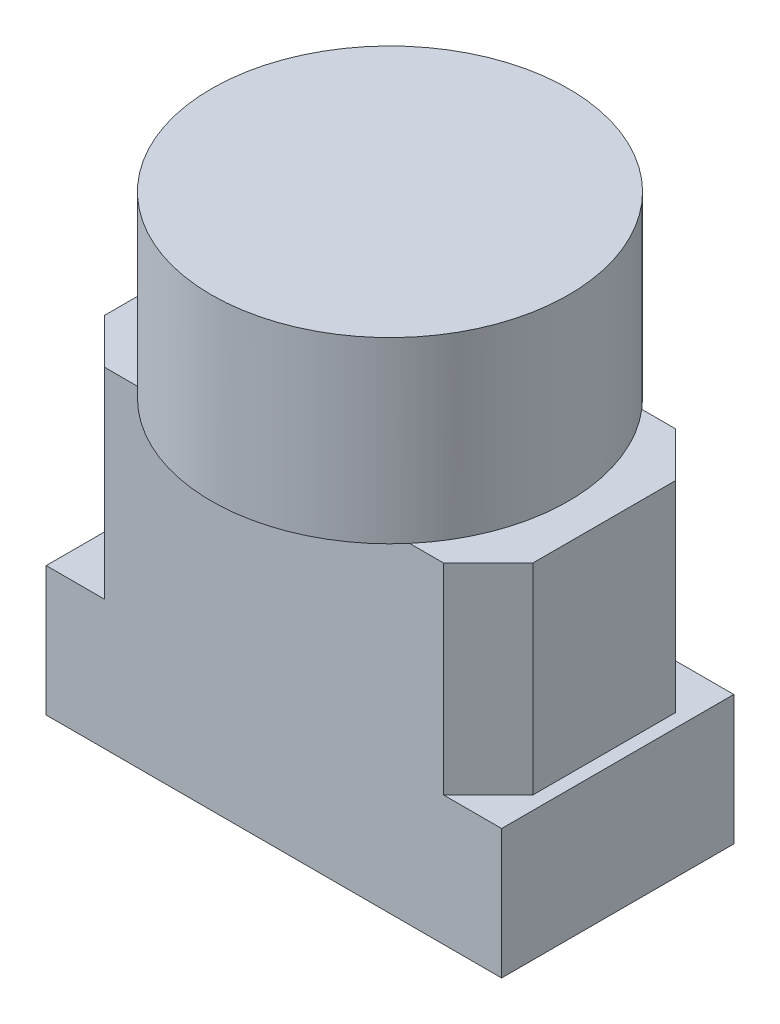
SolidWorks part; units mm, degrees
material "1060 Alloy"
ref_plane "Front Plane" through (0, 0, 0) normal (0, 0, 1) x (1, 0, 0)
ref_plane "Top Plane" through (0, 0, 0) normal (0, 1, 0) x (1, 0, 0)
ref_plane "Right Plane" through (0, 0, 0) normal (1, 0, 0) x (0, 0, -1)
sketch "Sketch1" plane through (0, 0, 0) normal (0, 1, 0) x (1, 0, 0)
  circle A0 centre (0, 0) radius 40
  dimension "D1" = 80
extrude "Boss-Extrude1" add sketch "Sketch1" along normal blind 40
sketch "Sketch2" plane through (0, 0, 0) normal (0, -1, 0) x (1, 0, 0)
  line L1 (48, 26) -> (-48, 26)
  line L2 (48, 26) -> (48, -26)
  line L3 (48, -26) -> (-48, -26)
  line L4 (-48, 26) -> (-48, -26)
  line L5 (48, 26) -> (-48, -26) construction
  line L6 (48, -26) -> (-48, 26) construction
  point P0 (0, 0)
  dimension "D1" = 96
  dimension "D2" = 52
extrude "Boss-Extrude2" add sketch "Sketch2" along normal blind 45
chamfer "Chamfer1" distance 10 angle 45 4 edges at (-48, -22.5, 26) (48, -22.5, 26) (-48, -22.5, -26) (48, -22.5, -26)
ref_point "Point1"
sketch "Sketch4" plane through (0, -45, 0) normal (0, -1, 0) x (-1, 0, 0)
  line L0 (38, 26) -> (-38, 26) construction
  line L1 (-51, -26) -> (51, -26)
  line L2 (-51, -26) -> (-51, 26)
  line L3 (-51, 26) -> (51, 26)
  line L4 (51, -26) -> (51, 26)
  line L5 (-51, -26) -> (51, 26) construction
  line L6 (-51, 26) -> (51, -26) construction
  point P0 (0, 0)
  dimension "D1" = 102
extrude "Boss-Extrude3" add sketch "Sketch4" along normal blind 33
chamfer "Chamfer2" distance 4 angle 45 4 edges at (51, -78, 0) (0, -78, 26) (-51, -78, 0) (0, -78, -26)
ref_point "gripper_base_point"
ref_axis "gripper_base_axis" through (0, 40, 0) along (0, -1, 0)
